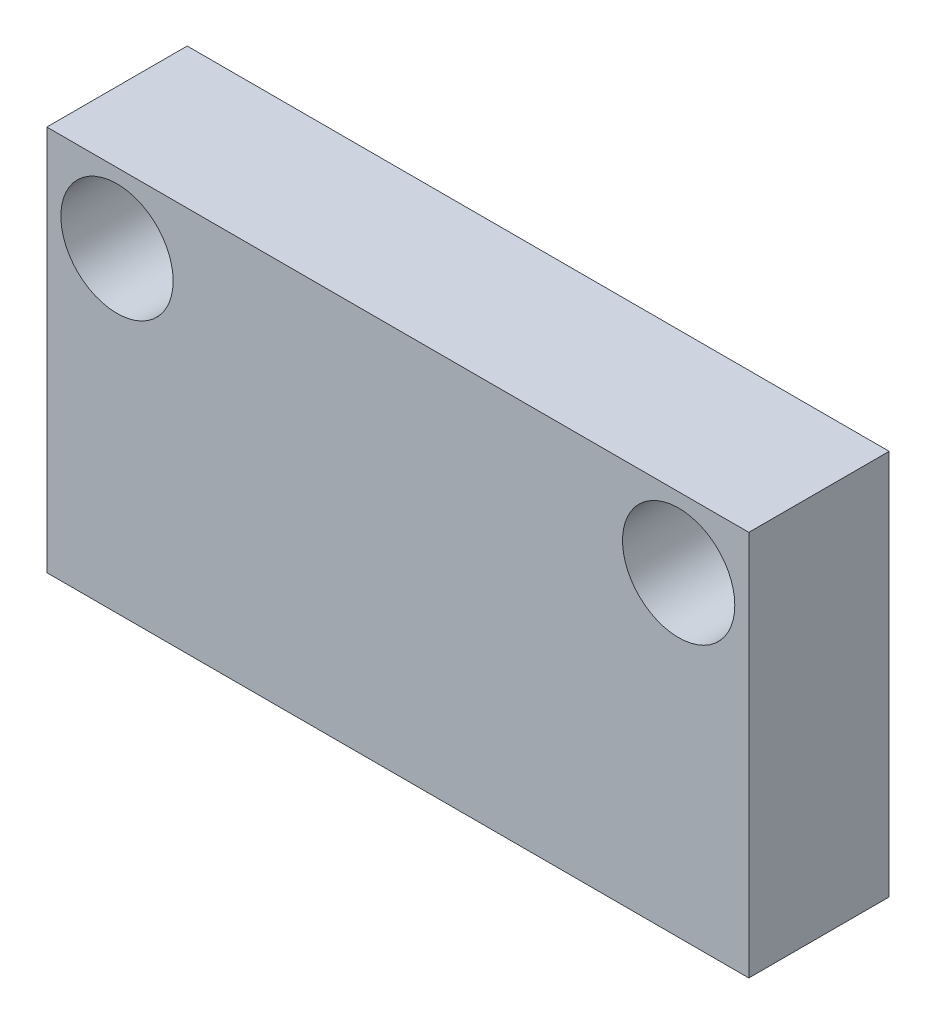
SolidWorks part; units mm, degrees
ref_plane "Front Plane" through (0, 0, 0) normal (0, 0, 1) x (1, 0, 0)
ref_plane "Top Plane" through (0, 0, 0) normal (0, 1, 0) x (1, 0, 0)
ref_plane "Right Plane" through (0, 0, 0) normal (1, 0, 0) x (0, 0, -1)
sketch "Sketch1" plane through (0, 0, 0) normal (0, 0, 1) x (1, 0, 0)
  line L1 (20.6185, 8) -> (40.6261, 8)
  line L2 (20.6185, 8) -> (20.6185, -3)
  line L3 (20.6185, -3) -> (40.6261, -3)
  line L4 (40.6261, 8) -> (40.6261, -3)
extrude "Boss-Extrude1" add sketch "Sketch1" along normal blind 4
hole_wizard "M3 Clearance Hole1" positions "Sketch3" profile "Sketch2" hole size "M3" standard "ISO" end condition through all
sketch "Sketch3" plane through (0, 0, 4) normal (0, 0, 1) x (1, 0, 0)
  point P0 (38.6261, 6)
  point P3 (22.6185, 6)
sketch "Sketch2" plane through (38.6261, 6, 4) normal (1, 0, 0) x (0, -1, 0)
  line L0 (0, 0) -> (0, 4)
  line L1 (0, 4) -> (1.6, 4)
  line L2 (1.6, 4) -> (1.6, 0)
  line L5 (1.6, 0) -> (0, 0)
  line L11 (0, -6.35) -> (0, 107.95) construction
  dimension "Thru Hole Dia." = 3.2
  dimension "Thru Hole Depth" = 4
